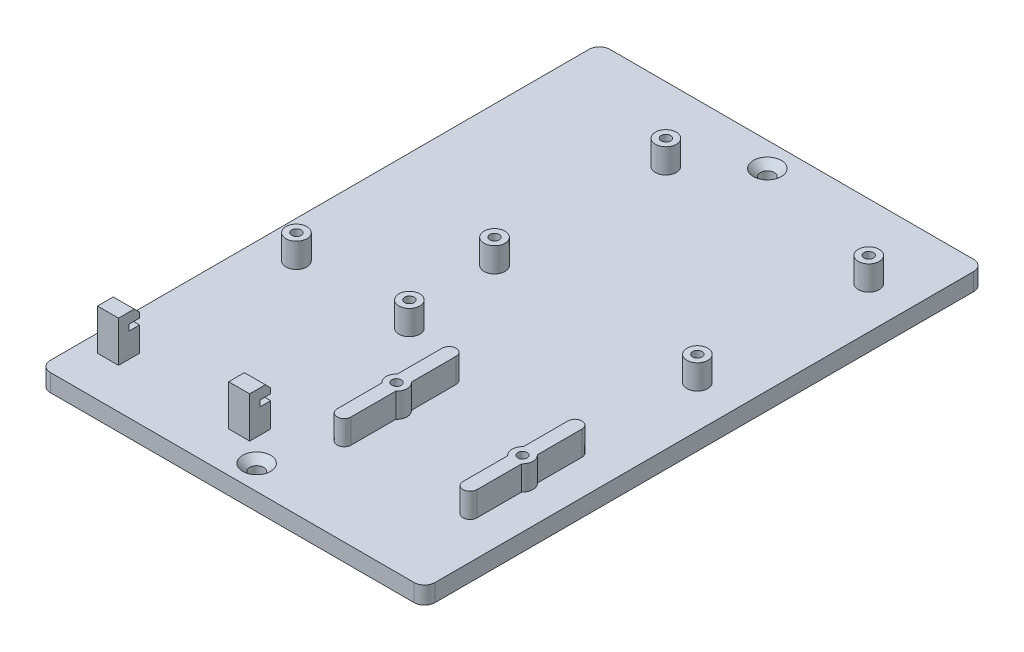
SolidWorks part; units mm, degrees
ref_plane "前视基准面" through (0, 0, 0) normal (0, 0, 1) x (1, 0, 0)
ref_plane "上视基准面" through (0, 0, 0) normal (0, 1, 0) x (1, 0, 0)
ref_plane "右视基准面" through (0, 0, 0) normal (1, 0, 0) x (0, 0, -1)
sketch "草图1" plane through (0, 0, 0) normal (0, 1, 0) x (1, 0, 0)
  line L0 (110, -80) -> (0, -80) construction
  line L1 (3, 0) -> (107, 0)
  line L2 (0, -3) -> (0, -157)
  line L3 (3, -160) -> (107, -160)
  line L4 (110, -3) -> (110, -157)
  line L5 (98, -21) -> (98, -70) construction
  line L6 (100, -122.2361) -> (100, -135)
  line L8 (96, -105) -> (96, -117.7639)
  line L10 (100, -105) -> (100, -117.7639)
  line L11 (96, -105) -> (100, -135) construction
  line L12 (96, -135) -> (100, -105) construction
  line L13 (96, -122.2361) -> (96, -135)
  line L14 (64, -122.2361) -> (64, -135)
  line L15 (60, -105) -> (60, -117.7639)
  line L16 (64, -105) -> (64, -117.7639)
  line L17 (60, -122.2361) -> (60, -135)
  line L18 (60, -105) -> (64, -135) construction
  line L19 (60, -135) -> (64, -105) construction
  arc A0 (3, -160) -> (0, -157) centre (3, -157) cw
  arc A1 (107, -160) -> (110, -157) centre (107, -157) ccw
  arc A2 (110, -3) -> (107, 0) centre (107, -3) ccw
  arc A3 (3, 0) -> (0, -3) centre (3, -3) ccw
  circle A4 centre (55, -7) radius 2
  circle A5 centre (55, -153) radius 2
  circle A6 centre (98, -21) radius 1.35
  circle A7 centre (98, -21) radius 3
  circle A8 centre (40, -21) radius 3
  circle A9 centre (40, -21) radius 1.35
  circle A10 centre (40, -70) radius 3
  circle A11 centre (40, -70) radius 1.35
  circle A12 centre (98, -70) radius 3
  circle A13 centre (98, -70) radius 1.35
  circle A14 centre (98, -120) radius 1.35
  arc A15 (100, -122.2361) -> (100, -117.7639) centre (98, -120) ccw
  arc A16 (100, -105) -> (96, -105) centre (98, -105) ccw
  arc A17 (96, -135) -> (100, -135) centre (98, -135) ccw
  arc A18 (96, -117.7639) -> (96, -122.2361) centre (98, -120) ccw
  circle A19 centre (62, -120) radius 1.35
  arc A20 (64, -122.2361) -> (64, -117.7639) centre (62, -120) ccw
  arc A21 (64, -105) -> (60, -105) centre (62, -105) ccw
  arc A22 (60, -135) -> (64, -135) centre (62, -135) ccw
  arc A23 (60, -117.7639) -> (60, -122.2361) centre (62, -120) ccw
  circle A24 centre (10, -142) radius 1.35 construction
  circle A25 centre (10, -142) radius 3 construction
  circle A26 centre (43.5, -142) radius 1.35 construction
  circle A27 centre (43.5, -142) radius 3 construction
  circle A28 centre (10.5661, -97.2036) radius 1.35
  circle A29 centre (10.5661, -97.2036) radius 3
  circle A30 centre (43.3624, -97.7002) radius 1.35
  circle A31 centre (43.3624, -97.7002) radius 3
  point P7 (0, -160)
  point P12 (110, 0)
  point P15 (0, 0)
  dimension "D3" = 3
  dimension "D4" = 4
  dimension "D7" = 2.7
  dimension "D8" = 6
  dimension "D14" = 2.7
  dimension "D15" = 6
  dimension "D23" = 2.7
  dimension "D24" = 6
  dimension "D1" = 160
  dimension "D2" = 110
  dimension "D5" = 7
  dimension "D6" = 55
  dimension "D9" = 12
  dimension "D10" = 21
  dimension "D13" = 49
  dimension "D16" = 12
  dimension "D17" = 40
  dimension "D18" = 4
  dimension "D19" = 30
  dimension "D21" = 10
  dimension "D22" = 18
  dimension "D25" = 33.5
  dimension "D26" = 44.8
  dimension "D27" = 55.6
  dimension "D28" = 32.8
  dimension "D29" = 44.3
  dimension "D11" = 2
  dimension "D12" = 2
  dimension "D20" = 2
extrude "凸台-拉伸1" add sketch "草图1" against normal blind 5 contours L1 A3 L2 A0 L3 A1 L4 A2 A31 A29 A23 L15 A21 L16 A20 L14 A22 L17 A18 L8 A16 L10 A15 L6 A17 L13 A12 A10 A8 A7 A4 A5 | A29 A28 | A10 A11 | A31 A30 | L15 A23 L17 A22 L14 A20 L16 A21 A19 | L8 A18 L13 A17 L6 A15 L10 A16 A14 | A12 A13 | A7 A6 | A8 A9 region at (54.5949, 0, 79.5218) region at (99.6547, 0, 128.618) region at (63.6547, 0, 128.618) region at (95.0849, 0, 21) region at (37.0849, 0, 21) region at (37.0849, 0, 70) region at (95.0849, 0, 70) region at (7.651, 0, 97.2036) region at (40.4472, 0, 97.7002)
extrude "凸台-拉伸2" add sketch "草图1<3>" along normal blind 7 contours A8 A9 | A7 A6 | A12 A13 | A10 A11 | A31 A30 | A29 A28 | L15 A23 L17 A22 L14 A20 L16 A21 A19 | L8 A18 L13 A17 L6 A15 L10 A16 A14 region at (99.6547, 0, 128.618) region at (63.6547, 0, 128.618) region at (95.0849, 0, 21) region at (37.0849, 0, 21) region at (37.0849, 0, 70) region at (95.0849, 0, 70) region at (7.651, 0, 97.2036) region at (40.4472, 0, 97.7002)
sketch "草图1<3>" plane through (0, 0, 0) normal (0, 1, 0) x (1, 0, 0) same geometry as "草图1"
chamfer "倒角1" distance 2 1 edges at (55, 0, 9)
chamfer "倒角2" distance 2 1 edges at (55, 0, 155)
sketch "草图3" plane through (0, 0, 0) normal (-1, 0, 0) x (0, 0, 1)
  line L0 (142, 0) -> (142.5, 0) construction
  line L1 (155, 0) -> (151, 0) construction
  line L2 (142.5, 0) -> (142.5, 7)
  line L3 (142.5, 7) -> (145.5, 7)
  line L4 (145.5, 7) -> (145.5, 8.7)
  line L5 (145.5, 8.7) -> (142.5, 8.7)
  line L6 (142.5, 8.7) -> (142.5, 10.2)
  line L7 (144, 11.7) -> (148.5, 11.7)
  line L8 (148.5, 11.7) -> (148.5, 0)
  line L9 (3, 0) -> (157, 0) construction
  line L10 (148.5, 0) -> (142.5, 0)
  line L11 (142.5, 10.2) -> (144, 11.7)
  line L12 (3, 0) -> (157, 0) construction
  line L13 (157, 0) -> (142, 0) construction
  point P9 (142.5, 11.7)
  point P15 (0, 0)
  point P16 (0, 0)
  dimension "D1" = 0.5
  dimension "D2" = 7
  dimension "D3" = 1.7
  dimension "D4" = 3
  dimension "D5" = 6
  dimension "D6" = 3
  dimension "D7" = 15
extrude "凸台-拉伸3" add sketch "草图3" against normal blind 50
sketch "草图4" plane through (0, 0, 148.5) normal (0, 0, 1) x (1, 0, 0)
  line L0 (50, 11.7) -> (0, 11.7) construction
  line L1 (0, 0) -> (5, 0)
  line L2 (0, 0) -> (0, 11.7)
  line L3 (0, 11.7) -> (5, 11.7)
  line L4 (5, 0) -> (5, 11.7)
  line L5 (3, 0) -> (107, 0) construction
  line L6 (11, 0) -> (42.5, 0)
  line L7 (11, 0) -> (11, 11.7)
  line L8 (11, 11.7) -> (42.5, 11.7)
  line L9 (42.5, 0) -> (42.5, 11.7)
  line L11 (50, 0) -> (48.5, 0)
  line L12 (50, 0) -> (50, 11.7)
  line L13 (50, 11.7) -> (48.5, 11.7)
  line L14 (48.5, 0) -> (48.5, 11.7)
  dimension "D1" = 5
  dimension "D2" = 6
  dimension "D3" = 31.5
  dimension "D4" = 6
extrude "切除-拉伸1" cut sketch "草图4" against normal blind 12
